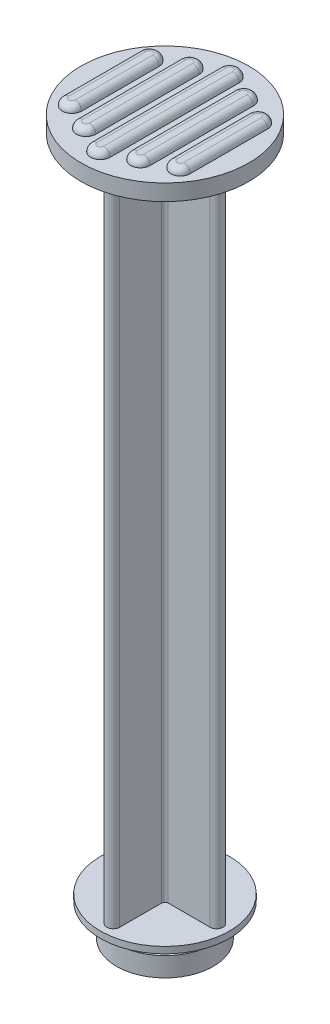
SolidWorks part; units mm, degrees
ref_plane "Front Plane" through (0, 0, 0) normal (0, 0, 1) x (1, 0, 0)
ref_plane "Top Plane" through (0, 0, 0) normal (0, 1, 0) x (1, 0, 0)
ref_plane "Right Plane" through (0, 0, 0) normal (1, 0, 0) x (0, 0, -1)
sketch "Sketch1" plane through (0, 0, 0) normal (0, 0, 1) x (1, 0, 0)
  line L0 (0, 0) -> (7.5, 0)
  line L1 (7.5, 0) -> (7.5, 3)
  line L2 (7.5, 3) -> (6, 3)
  line L3 (6, 3) -> (6, 5)
  line L4 (6, 5) -> (10, 5)
  line L5 (10, 5) -> (10, 6)
  line L6 (10, 6) -> (0, 6)
  line L7 (0, 6) -> (0, 0)
  dimension "D1" = 7.5
  dimension "D2" = 3
  dimension "D3" = 2
  dimension "D4" = 1
  dimension "D5" = 10
  dimension "D6" = 6
revolve "Revolve1" add sketch "Sketch1" angle 360 about L7
sketch "Sketch2" plane through (0, 6, 0) normal (0, 1, 0) x (1, 0, 0)
  line L0 (0, 10) -> (0, -10) construction
  line L1 (-10, 0) -> (10, 0) construction
  line L2 (-1, 8) -> (-1, 1.5)
  line L3 (-8, -1) -> (-1.5, -1)
  line L4 (1, 8) -> (1, 1.5)
  line L5 (-8, 1) -> (-1.5, 1)
  line L6 (1, 10) -> (1, -10) construction
  line L7 (-1, 10) -> (-1, -10) construction
  line L8 (-10, 1) -> (10, 1) construction
  line L9 (-10, -1) -> (10, -1) construction
  line L10 (1.5, -1) -> (8, -1)
  line L11 (1, -1.5) -> (1, -8)
  line L12 (1.5, 1) -> (8, 1)
  line L13 (-1, -1.5) -> (-1, -8)
  circle A0 centre (0, 0) radius 10 construction
  arc A1 (1, 8) -> (-1, 8) centre (0, 8) ccw
  arc A2 (-8, 1) -> (-8, -1) centre (-8, 0) ccw
  arc A3 (8, 1) -> (8, -1) centre (8, 0) cw
  arc A4 (1, -8) -> (-1, -8) centre (0, -8) cw
  arc A5 (-1, -1.5) -> (-1.5, -1) centre (-1.5, -1.5) ccw
  arc A6 (1.5, -1) -> (1, -1.5) centre (1.5, -1.5) ccw
  arc A7 (1, 1.5) -> (1.5, 1) centre (1.5, 1.5) ccw
  arc A8 (-1.5, 1) -> (-1, 1.5) centre (-1.5, 1.5) ccw
  point P36 (1, -1)
  point P39 (1, 1)
  dimension "D3" = 8
  dimension "D5" = 0.5
  dimension "D4" = 8
  dimension "D1" = 1
  dimension "D2" = 1
extrude "Boss-Extrude1" add sketch "Sketch2" along normal blind 102
sketch "Sketch3" plane through (0, 108, 0) normal (0, 1, 0) x (1, 0, 0)
  circle A0 centre (0, 0) radius 13
  dimension "D1" = 26
extrude "Boss-Extrude2" add sketch "Sketch3" along normal blind 2.5
sketch "Sketch4" plane through (0, 110.5, 0) normal (0, 1, 0) x (1, 0, 0)
  line L0 (0, 13) -> (0, -13) construction
  line L1 (-13, 0) -> (13, 0) construction
  line L2 (-4.2, 8) -> (-4.2, -8) construction
  line L3 (-8.4, 6) -> (-8.4, -6) construction
  line L4 (4.2, 8) -> (4.2, -8) construction
  line L5 (-1.5, 10) -> (-1.5, -10)
  line L6 (8.4, 6) -> (8.4, -6) construction
  line L7 (1.5, 10) -> (1.5, -10)
  line L8 (-5.7, 8) -> (-5.7, -8)
  line L9 (-9.9, 6) -> (-9.9, -6)
  line L10 (-2.7, 8) -> (-2.7, -8)
  line L11 (-6.9, 6) -> (-6.9, -6)
  line L12 (-1.5, 13) -> (-1.5, -13) construction
  line L13 (1.5, 13) -> (1.5, -13) construction
  line L14 (9.9, 6) -> (9.9, -6)
  line L15 (6.9, 6) -> (6.9, -6)
  line L16 (5.7, 8) -> (5.7, -8)
  line L17 (2.7, 8) -> (2.7, -8)
  circle A0 centre (0, 0) radius 13 construction
  arc A1 (-2.7, 8) -> (-5.7, 8) centre (-4.2, 8) ccw
  arc A2 (-6.9, 6) -> (-9.9, 6) centre (-8.4, 6) ccw
  arc A3 (-9.9, -6) -> (-6.9, -6) centre (-8.4, -6) ccw
  arc A4 (-5.7, -8) -> (-2.7, -8) centre (-4.2, -8) ccw
  arc A5 (-1.5, -10) -> (1.5, -10) centre (0, -10) ccw
  arc A6 (1.5, 10) -> (-1.5, 10) centre (0, 10) ccw
  arc A7 (6.9, 6) -> (9.9, 6) centre (8.4, 6) cw
  arc A8 (9.9, -6) -> (6.9, -6) centre (8.4, -6) cw
  arc A9 (5.7, -8) -> (2.7, -8) centre (4.2, -8) cw
  arc A10 (2.7, 8) -> (5.7, 8) centre (4.2, 8) cw
  dimension "D1" = 1.5
  dimension "D3" = 8.4
  dimension "D4" = 6
  dimension "D2" = 4.2
  dimension "D5" = 10
extrude "Boss-Extrude3" add sketch "Sketch4" along normal blind 1
fillet "Fillet1" radius 1 20 edges at (9.9, 111.5, 0) (8.4, 111.5, 7.5) (6.9, 111.5, 0) (8.4, 111.5, -7.5) (5.7, 111.5, 0) (4.2, 111.5, 9.5) (2.7, 111.5, 0) (4.2, 111.5, -9.5) (1.5, 111.5, 0) (0, 111.5, 11.5) (-1.5, 111.5, 0) (0, 111.5, -11.5) (-2.7, 111.5, 0) (-4.2, 111.5, 9.5) (-5.7, 111.5, 0) (-4.2, 111.5, -9.5) (-6.9, 111.5, 0) (-8.4, 111.5, 7.5) (-9.9, 111.5, 0) (-8.4, 111.5, -7.5)
